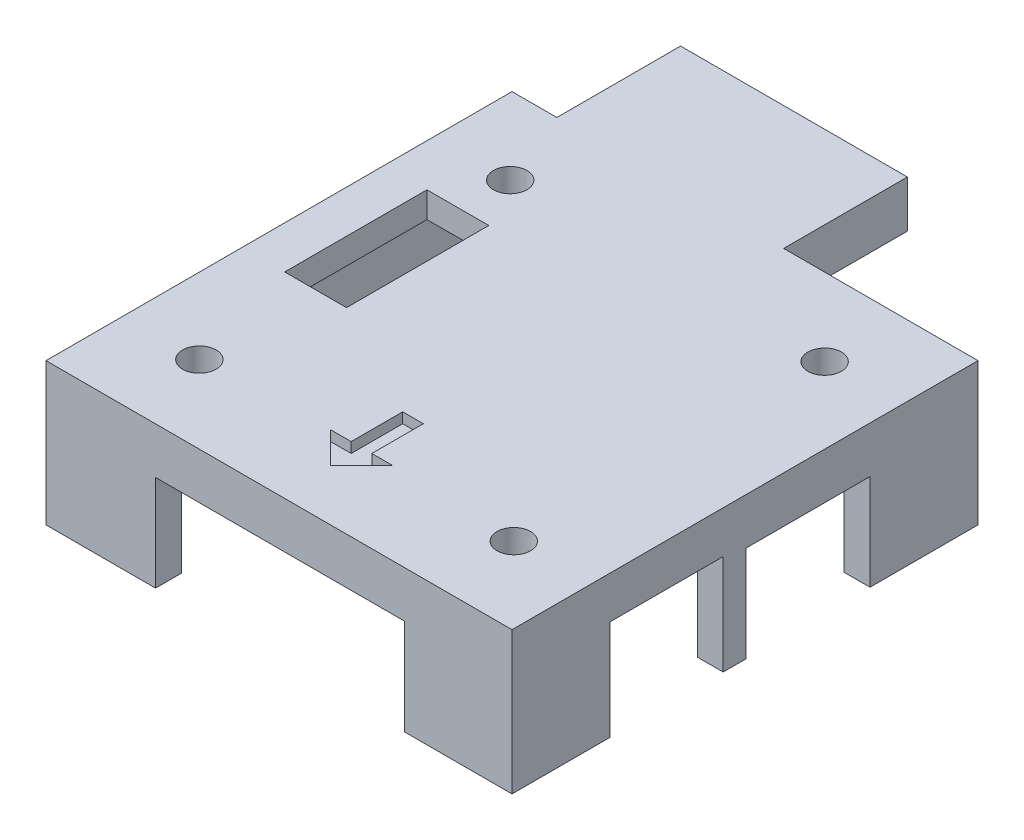
SolidWorks part; units mm, degrees
ref_plane "Front Plane" through (0, 0, 0) normal (0, 0, 1) x (1, 0, 0)
ref_plane "Top Plane" through (0, 0, 0) normal (0, 1, 0) x (1, 0, 0)
ref_plane "Right Plane" through (0, 0, 0) normal (1, 0, 0) x (0, 0, -1)
sketch "Sketch2" plane through (0, 0, 0) normal (0, 1, 0) x (1, 0, 0)
  line L0 (0, -106.5655) -> (0, -83.7637) construction
  line L1 (0, -83.7637) -> (0, -93.9153) construction
  line L2 (15.25, -15.075) -> (15.25, 15.075) construction
  line L3 (15.25, -15.075) -> (-15.25, -15.075) construction
  line L4 (15.25, 15.075) -> (-15.25, 15.075) construction
  line L5 (-15.25, -15.075) -> (-15.25, 15.075) construction
  line L6 (15.25, -15.075) -> (-15.25, 15.075) construction
  line L7 (15.25, 15.075) -> (-15.25, -15.075) construction
  line L8 (-22.6, -22.6) -> (-22.6, 22.6)
  line L9 (-20.1, -20.1) -> (20.1, -20.1)
  line L10 (-20.1, -20.1) -> (-20.1, 20.1)
  line L11 (-20.1, 20.1) -> (20.1, 20.1)
  line L12 (20.1, -20.1) -> (20.1, 20.1)
  line L13 (-20.1, -20.1) -> (20.1, 20.1) construction
  line L14 (-20.1, 20.1) -> (20.1, -20.1) construction
  line L15 (-22.6, 22.6) -> (22.6, 22.6)
  line L16 (22.6, -22.6) -> (22.6, 22.6)
  line L17 (-22.6, -22.6) -> (22.6, -22.6)
  circle A0 centre (-15.25, -15.075) radius 1.625
  circle A1 centre (-15.25, 15.075) radius 1.625
  circle A2 centre (15.25, 15.075) radius 1.625
  circle A3 centre (15.25, -15.075) radius 1.625
  point P4 (0, 0)
  point P14 (0, 0)
  dimension "D3" = 3.25
  dimension "D1" = 30.5
  dimension "D2" = 30.15
  dimension "D4" = 40.2
  dimension "D5" = 40.2
  dimension "D6" = 2.5
extrude "Top" add sketch "Sketch2" along normal blind 2.5 contours L8 L17 L16 L15 L12 L9 L10 L11 | L9 L12 L11 L10 A3 A2 A1 A0 region at (-21.9608, 0, 0) region at (0, 0, 0)
extrude "Side Walls" add sketch "Sketch2<3>" against normal blind 11.3 contours L8 L17 L16 L15 L12 L9 L10 L11 region at (-21.9608, 0, 0)
sketch "Sketch2<3>" plane through (0, 0, 0) normal (0, 1, 0) x (1, 0, 0) same geometry as "Sketch2"
sketch "Sketch3" plane through (0, 2.5, 0) normal (0, 1, 0) x (1, 0, 0)
  line L0 (0, 0) -> (0, -22.6) construction
  line L1 (-22.6, -22.6) -> (22.6, -22.6) construction
  line L2 (0, -17.6) -> (3, -14.6)
  line L3 (3, -14.6) -> (1, -14.6)
  line L4 (1, -14.6) -> (1, -9.6)
  line L5 (1, -9.6) -> (-1, -9.6)
  line L6 (0, -17.6) -> (-3, -14.6)
  line L7 (-3, -14.6) -> (-1, -14.6)
  line L8 (-1, -14.6) -> (-1, -9.6)
  point P13 (0, -9.6)
  dimension "D1" = 45
  dimension "D2" = 1
  dimension "D3" = 5
  dimension "D4" = 5
extrude "Direction Indicator" cut sketch "Sketch3" against normal blind 1
sketch "Sketch4" plane through (0, 0, 22.6) normal (0, 0, 1) x (1, 0, 0)
  line L0 (-19.975, 0) -> (19.975, 0) construction
  line L1 (-19.975, 1.7) -> (19.975, 1.7) construction
  line L2 (-11.975, -2) -> (-0.375, -2)
  line L3 (-11.975, -2) -> (-11.975, -12.6)
  line L4 (-0.375, -2) -> (-0.375, -11.3) construction
  line L5 (-22.6, -11.3) -> (22.6, -11.3) construction
  line L6 (-11.975, -12.6) -> (-11.975, -11.3)
  line L7 (-11.975, -11.3) -> (-0.375, -11.3)
  line L8 (12.175, -2) -> (12.175, -12.2461)
  line L9 (12.175, -2) -> (0.575, -2)
  line L10 (0.575, -2) -> (0.575, -12.2461) construction
  line L11 (0.575, -12.2461) -> (12.175, -12.2461)
  line L12 (0.575, -12.2461) -> (-0.375, -12.2461)
  line L13 (0.575, -2) -> (-0.375, -2)
  line L14 (-0.375, -12.2461) -> (-0.375, -11.3)
  point P3 (0, 0)
  line M13 (-22.6, -11.3) -> (22.6, -11.3)
  dimension "D1" = 39.95
  dimension "D2" = 1.7
  dimension "D3" = 3.7
  dimension "D4" = 8
  dimension "D5" = 11.6
  dimension "D6" = 10.6
  dimension "D7" = 7.8
  dimension "D8" = 11.6
  dimension "D9" = 3.7
extrude "Front Ports" cut sketch "Sketch4" against normal up to next contours L14 L12 L11 L8 L9 L13 L2 L3 M13 region at (0.1, -6.65, 22.6)
sketch "Sketch5" plane through (0, 2.5, 0) normal (0, 1, 0) x (1, 0, 0)
  line L0 (-18.475, -3.575) -> (-12.475, -3.575)
  line L1 (-19.975, -19.975) -> (19.975, -19.975) construction
  line L2 (-19.975, -19.975) -> (-19.975, 19.975) construction
  line L3 (-19.975, 19.975) -> (19.975, 19.975) construction
  line L4 (19.975, -19.975) -> (19.975, 19.975) construction
  line L5 (-19.975, -19.975) -> (19.975, 19.975) construction
  line L6 (-19.975, 19.975) -> (19.975, -19.975) construction
  line L7 (-12.475, -3.575) -> (-12.475, 10.225)
  line L8 (-12.475, 10.225) -> (-18.475, 10.225)
  line L9 (-18.475, 10.225) -> (-18.475, -3.575)
  point P0 (0, 0)
  dimension "D1" = 39.95
  dimension "D2" = 16.4
  dimension "D3" = 3
  dimension "D4" = 6
  dimension "D5" = 13.8
extrude "Wifi Port" cut sketch "Sketch5" against normal up to next
sketch "Sketch6" plane through (-22.6, 0, 0) normal (-1, 0, 0) x (0, 0, 1)
  line L0 (0, -0.3776) -> (0, -12.7435) construction
  line L1 (-19.975, 0) -> (19.975, 0) construction
  line L2 (-19.975, 1.7) -> (19.975, 1.7) construction
  line L3 (12.175, -2) -> (1.975, -2)
  line L4 (12.175, -2) -> (12.175, -11.3)
  line L5 (22.6, -11.3) -> (-22.6, -11.3) construction
  line L6 (12.175, -11.3) -> (1.975, -11.3)
  line L7 (1.975, -11.3) -> (1.975, -2)
  line L8 (-0.675, -7.55) -> (-12.225, -7.55)
  line L9 (-12.225, -7.55) -> (-12.225, -11.3)
  line L10 (-12.225, -11.3) -> (-0.675, -11.3)
  line L11 (-0.675, -11.3) -> (-0.675, -7.55)
  point P7 (0, 0)
  point P11 (0, 1.7)
  dimension "D1" = 39.95
  dimension "D2" = 1.7
  dimension "D3" = 3.7
  dimension "D4" = 10.2
  dimension "D5" = 7.8
  dimension "D6" = 9.25
  dimension "D7" = 7.75
  dimension "D8" = 11.55
extrude "Right Ports" cut sketch "Sketch6" against normal up to next
sketch "Sketch7" plane through (0, 0, -22.6) normal (0, 0, -1) x (-1, 0, 0)
  line L0 (-19.975, 0) -> (19.975, 0) construction
  line L1 (0, -15.6086) -> (0, 15.6086) construction
  line L2 (-19.975, 1.7) -> (19.975, 1.7) construction
  line L3 (22.6, 2.5) -> (22.6, -11.3) construction
  line L4 (15.25, 0) -> (-0.75, 0)
  line L5 (15.25, 0) -> (15.25, -11.3)
  line L6 (15.25, -11.3) -> (-0.75, -11.3)
  line L7 (-0.75, 0) -> (-0.75, -11.3)
  line L8 (-12.225, -2.05) -> (-12.225, -11.4)
  line L10 (-12.225, -2.05) -> (-0.75, -2.05)
  line L11 (-0.75, -2.05) -> (-0.75, -11.4)
  line L12 (-0.75, -11.4) -> (-12.225, -11.4)
  line L13 (22.6, -11.3) -> (-22.6, -11.3) construction
  point P4 (0, 0)
  point P8 (0, 0)
  point P11 (0, 1.7)
  line M10 (-22.6, -11.3) -> (22.6, -11.3)
  dimension "D1" = 39.95
  dimension "D2" = 1.7
  dimension "D3" = 7.35
  dimension "D4" = 16
  dimension "D6" = 7.75
  dimension "D7" = 3.75
  dimension "D8" = 9.35
extrude "Rear Ports" cut sketch "Sketch7" against normal up to next contours L11 L7 L10 L8 M10 | L5 L4 L7 L6 region at (6.4875, -6.675, -22.6)
sketch "Sketch8" plane through (22.6, 0, 0) normal (1, 0, 0) x (0, 0, -1)
  line L0 (0, -0.1576) -> (0, -7.3362) construction
  line L1 (-19.975, 0) -> (19.975, 0) construction
  line L2 (-19.975, 1.7) -> (19.975, 1.7) construction
  line L3 (-12.125, -3.7) -> (-12.125, -7.5) construction
  line L4 (-12.125, -7.5) -> (-3.1114, -7.5) construction
  line L5 (-3.1114, -7.5) -> (-3.1114, -3.7) construction
  line L6 (-3.1114, -3.7) -> (-12.125, -3.7) construction
  line L7 (0.075, -2) -> (12.125, -2)
  line L8 (12.125, -2) -> (12.125, -11.3)
  line L9 (12.125, -11.3) -> (0.075, -11.3)
  line L10 (0.075, -11.3) -> (0.075, -2)
  line L11 (-22.6, -11.3) -> (22.6, -11.3) construction
  line L12 (-7.6182, -3.7) -> (-7.6182, -7.5) construction
  line L13 (-13.1182, -9.6) -> (-13.1182, -15.8962)
  line L14 (-13.1182, -9.6) -> (-2.1182, -9.6) construction
  line L15 (-13.1182, -9.6) -> (-13.1182, -1.6)
  line L16 (-13.1182, -1.6) -> (-2.1182, -1.6)
  line L17 (-2.1182, -9.6) -> (-2.1182, -1.6)
  line L18 (-13.1182, -9.6) -> (-2.1182, -1.6) construction
  line L19 (-13.1182, -1.6) -> (-2.1182, -9.6) construction
  line L20 (-13.1182, -15.8962) -> (-2.1182, -15.8962)
  line L21 (-2.1182, -15.8962) -> (-2.1182, -9.6)
  point P7 (0, 0)
  point P11 (0, 1.7)
  point P21 (-7.6182, -5.6)
  dimension "D1" = 39.95
  dimension "D2" = 1.7
  dimension "D3" = 7.85
  dimension "D4" = 5.4
  dimension "D5" = 3.8
  dimension "D6" = 12.05
  dimension "D7" = 3.7
  dimension "D8" = 7.85
  dimension "D9" = 8
  dimension "D10" = 11
extrude "Left Ports" cut sketch "Sketch8" against normal up to next
sketch "Sketch9" plane through (0, 0, -22.6) normal (0, 0, -1) x (-1, 0, 0)
  line L0 (-0.75, -2.05) -> (-3.75, -2.05)
  line L1 (-12.225, -2.05) -> (-0.75, -2.05) construction
  line L2 (-3.75, -2.05) -> (-3.75, 2.5)
  line L3 (22.6, 2.5) -> (-22.6, 2.5) construction
  line L4 (-3.75, 2.5) -> (18.25, 2.5)
  line L5 (18.25, 2.5) -> (18.25, -11.3)
  line L6 (22.6, -11.3) -> (15.25, -11.3) construction
  line L7 (18.25, -11.3) -> (16.25, -11.3)
  line L8 (16.25, -11.3) -> (16.25, 1)
  line L9 (16.25, 1) -> (-1.75, 1)
  line L10 (-1.75, 1) -> (-1.75, -2.05)
  line L11 (15.25, 0) -> (-0.75, 0) construction
  line L12 (-0.75, 0) -> (-0.75, -2.05) construction
  line L13 (15.25, 0) -> (15.25, -11.3) construction
  line M8 (15.25, -11.3) -> (22.6, -11.3)
  line M10 (22.6, 2.5) -> (-22.6, 2.5)
  line M14 (-12.225, -2.05) -> (-0.75, -2.05)
  dimension "D1" = 1
  dimension "D2" = 1
  dimension "D3" = 1
  dimension "D4" = 2
  dimension "D5" = 2
extrude "Boss-Extrude3" add sketch "Sketch9" along normal blind 12 contours L10 L9 L8 L5 L2 M8 M10 M14 region at (2.75, -1.7903, -22.6)
